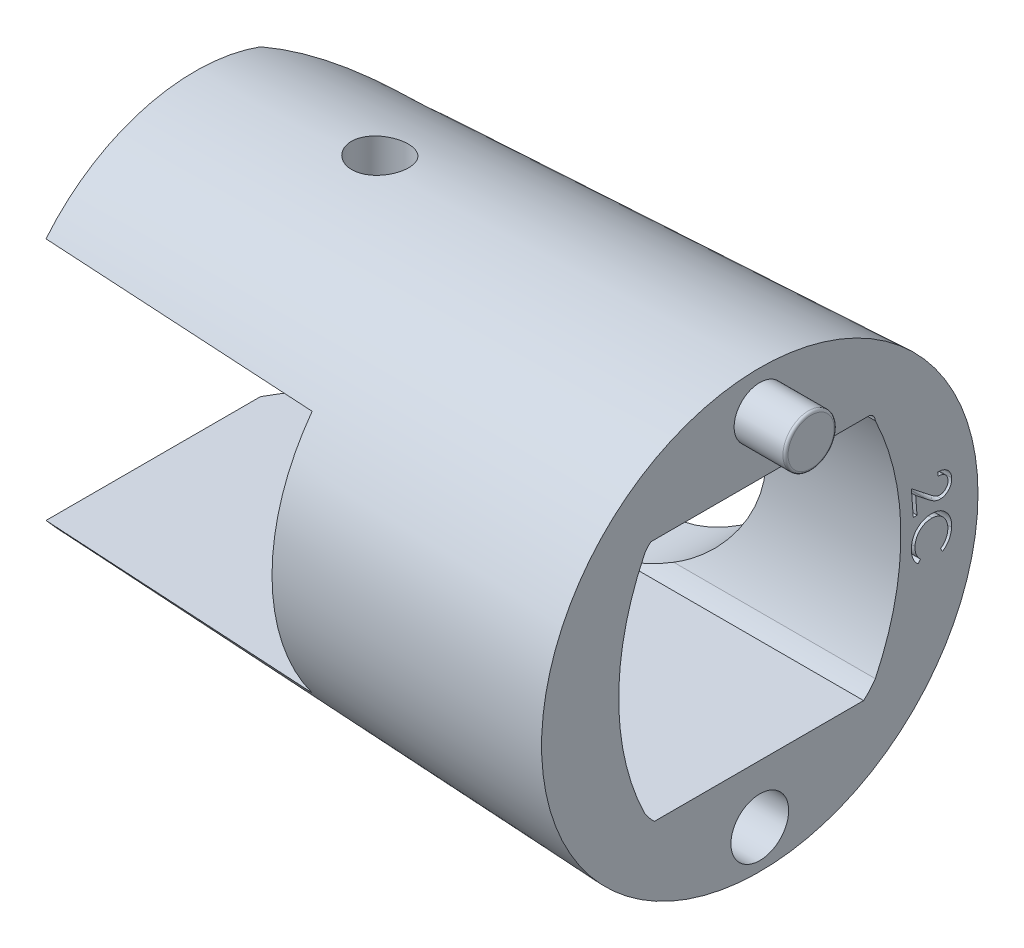
SolidWorks part; units mm, degrees
ref_plane "Front Plane" through (0, 0, 0) normal (0, 0, 1) x (1, 0, 0)
ref_plane "Top Plane" through (0, 0, 0) normal (0, 1, 0) x (1, 0, 0)
ref_plane "Right Plane" through (0, 0, 0) normal (1, 0, 0) x (0, 0, -1)
sketch "Sketch1" plane through (0, 0, 0) normal (0, 1, 0) x (1, 0, 0)
  line L0 (0, 0) -> (-22, 0)
  dimension "D1" = 22
ref_plane "Plane1" through (-22, 0, 0) normal (1, 0, 0) x (0, 0, -1)
sketch "Sketch2" plane through (-22, 0, 0) normal (1, 0, 0) x (0, 0, -1)
  circle A0 centre (0, 0) radius 7.5
  dimension "D1" = 15
sketch "Sketch3" plane through (0, 0, 0) normal (1, 0, 0) x (0, 0, -1)
  circle A0 centre (0, 0) radius 8.5
  dimension "D1" = 17
loft "Loft1" add profiles "Sketch2", "Sketch3" connector at (-22, 0, -7.5) connector at (0, 0, -8.5)
sketch "Sketch4" plane through (0, 0, 0) normal (0, 0, 1) x (1, 0, 0)
  line L0 (0, 0) -> (-10, 0) construction
  line L1 (-26.5378, 4.75) -> (-11, 4.75)
  line L2 (-26.5378, 4.75) -> (-26.5378, -4.75)
  line L3 (-26.5378, -4.75) -> (-11, -4.75)
  line L4 (-11, 4.75) -> (-11, -4.75)
  line L5 (0, 0) -> (-22, 0) construction
  line L6 (0, -8.5) -> (0, 8.5) construction
  point P12 (-11, 0)
  dimension "D1" = 10
  dimension "D2" = 11
  dimension "D3" = 9.5
  dimension "D4" = 15.5378
extrude "Cut-Extrude1" cut sketch "Sketch4" against normal blind 10 and the other way blind 10
sketch "Sketch5" plane through (0, 0, 0) normal (0, 1, 0) x (1, 0, 0)
  line L1 (-11, -6.7777) -> (-23.0023, -6.0429)
  line L2 (-23.0023, -6.0429) -> (-23.0231, -1.4883)
  line L3 (-11, 6.9546) -> (-14.8219, 6.8903)
  line L4 (-11, 8.5741) -> (-11, -8.5015)
  line L7 (-26, -8.5015) -> (-11, -8.5015)
  line L8 (0, 0) -> (-4.8047, 0) construction
  line L9 (0, 8.5) -> (-11, 8.5741) construction
  line L10 (0, -8.5) -> (-11, -8.5015) construction
  line L11 (-26, 8.5015) -> (-11, 8.5015)
  line L12 (-26, 8.5015) -> (-26, -8.5015)
  arc A0 (-14.8219, 6.8903) -> (-23.0231, -1.4883) centre (-14.6815, -1.4502) ccw
  dimension "D4" = 8.3417
  dimension "D11" = 3.8219
  dimension "D1" = 86.496
  dimension "D2" = 89.035
  dimension "D3" = 93.765
  dimension "D5" = 12.0231
  dimension "D6" = 4.5546
  dimension "D7" = 15
  dimension "D8" = 11
  dimension "D9" = 12.0023
  dimension "D10" = 17.003
  dimension "D12" = 1.7238
extrude "Cut-Extrude2" cut sketch "Sketch5" against normal blind 10 and the other way blind 10 contours A0 L3 L7 L1 L2 region at (-11.2267, 0, 7.6396)
sketch "Sketch6" plane through (0, 0, 0) normal (0, 1, 0) x (1, 0, 0)
  line L0 (-11, -8) -> (-15.3, -8) construction
  line L1 (-15.3, 0.5) -> (-15.3, -8) construction
  circle A0 centre (-15.3, 0.5) radius 1.05
  dimension "D1" = 2.1
  dimension "D2" = 4.3
  dimension "D3" = 8.5
extrude "Cut-Extrude3" cut sketch "Sketch6" against normal through all both and the other way through all
sketch "Sketch7" plane through (0, 0, 0) normal (1, 0, 0) x (0, 0, -1)
  line L2 (0, 25.5) -> (0, -8.5) construction
  line L5 (-8.5, 0) -> (8.5, 0) construction
  line L6 (4.3126, 4.2776) -> (4.3126, -4.2776)
  line L7 (-4.3126, 4.2776) -> (-4.3126, -4.2776)
  arc A2 (4.3126, 4.2776) -> (-4.3126, 4.2776) centre (0, -5.2323) ccw
  circle A4 centre (0, 0) radius 8.5 construction
  arc A5 (4.3126, -4.2776) -> (-4.3126, -4.2776) centre (0, 5.2323) cw
  point P11 (-4.3126, 0)
  point P13 (0, 8.5)
  point P16 (0, 0)
  point P17 (4.3126, 0)
  dimension "D3" = 10.4421
  dimension "D1" = 4.2776
  dimension "D2" = 4.3126
sketch "Sketch8" plane through (0, 0, 0) normal (1, 0, 0) x (0, 0, -1)
  line L2 (-4.5, 4.439) -> (4.5, 4.461)
  line L3 (-4.5, -4.261) -> (4.5, -4.239)
  line L4 (-8.5, 0) -> (8.5, 0) construction
  line L5 (0, -8.5) -> (0, 8.7) construction
  line L6 (0, 8.7) -> (0, 5.4132) construction
  line L7 (-4.5, 4.439) -> (-4.5, -4.261) construction
  line L8 (4.5, 4.461) -> (4.5, -4.239) construction
  arc A2 (-4.5, 4.439) -> (-4.5, -4.261) centre (4.5043, 0.089) ccw
  arc A3 (4.5, 4.461) -> (4.5, -4.239) centre (-4.5043, 0.111) cw
  dimension "D1" = 10
  dimension "D7" = 8.5
  dimension "D9" = 4
  dimension "D2" = 9
  dimension "D3" = 4.5
  dimension "D4" = 8.7
  dimension "D5" = 8.7
  dimension "D6" = 4.25
  dimension "D8" = 4.25
  dimension "D10" = 4
extrude "Cut-Extrude4" cut sketch "Sketch8" against normal blind 12 and the other way through all
sketch "Croquis1" plane through (0, 0, 0) normal (1, 0, 0) x (0, 0, -1)
  line L0 (0, 8.5) -> (0, -8.5) construction
  line L2 (-8.5, 0) -> (8.5, 0) construction
  line L3 (9.4094, 0) -> (-9.4094, 0) construction
  circle A0 centre (0, 0) radius 8.5 construction
  circle A1 centre (0, -7) radius 1.125
  circle A2 centre (0, 7) radius 1
  point P4 (0, 0)
  point P13 (0, 0)
  dimension "D2" = 2.25
  dimension "D4" = 2
  dimension "D1" = 1.5
  dimension "D3" = 1.5
extrude "Saliente-Extruir1" add sketch "Croquis1" along normal blind 2 contours A2
extrude "Cortar-Extruir1" cut sketch "Croquis1<4>" against normal blind 2.15 contours A1
sketch "Croquis1<4>" plane through (0, 0, 0) normal (1, 0, 0) x (0, 0, -1) same geometry as "Croquis1"
fillet "Redondeo1" radius 0.1 1 edges at (2, 7, -1)
ref_plane "Plano1" through (0, 0, -8) normal (0, 0, 1) x (1, 0, 0)
sketch "Croquis2" plane through (0, 0, -8) normal (0, 0, 1) x (1, 0, 0)
  line L0 (-11, 4.75) -> (-11, -4.75)
  line L1 (-11, 4.75) -> (-10, 4.75)
  line L2 (-10, -4.75) -> (-11, -4.75)
  arc A0 (-10, 4.75) -> (-10, -4.75) centre (-10, 0) cw
  point P0 (-9.2775, 3.6345)
  point P1 (-8.2353, -5.1333)
  point P2 (-11, 4.75)
  point P3 (-11, -4.75)
  dimension "D1" = 1
extrude "Cortar-Extruir2" cut sketch "Croquis2" along normal mid plane 10
sketch "Croquis8" plane through (-11, 0, 0) normal (-1, 0, 0) x (0, 0, 1)
  line L0 (5.8041, 4.75) -> (-2.5526, 4.75) construction
  line L1 (-6.0137, 4.75) -> (-2.5526, 4.75) construction
  line L2 (-3, 4.4574) -> (4.5, 4.439) construction
  line L3 (-3, 4.75) -> (-3, 4.4574) construction
  line L4 (4.2309, 4.75) -> (-2.5526, 4.75)
  line L5 (-3, 4.75) -> (-2.5526, 4.75)
  line L6 (-3, 4.4574) -> (4.5, 4.439)
  line L7 (-3, 4.75) -> (-3, 4.4574)
  line L8 (6.4372, 4.75) -> (-3, 4.75) construction
  arc A0 (4.5, 4.439) -> (4.2309, 4.75) centre (3.8402, 4.14) ccw
  dimension "D2" = 6.7835
  dimension "D1" = 0.7244
extrude "Cortar-Extruir9" cut sketch "Croquis8" against normal mid plane 40
sketch "Croquis9" plane through (-11, 0, 0) normal (-1, 0, 0) x (0, 0, 1)
  line L0 (6.4372, -4.75) -> (-3, -4.75) construction
  line L1 (-3, -4.2427) -> (-3, -4.75) construction
  line L2 (4.5, -4.261) -> (-3, -4.2427) construction
  line L3 (4.1093, -4.75) -> (-3, -4.75)
  line L4 (-3, -4.2427) -> (-3, -4.75)
  line L5 (4.5, -4.261) -> (-3, -4.2427)
  arc A0 (4.5, -4.261) -> (4.1093, -4.75) centre (2.2668, -2.8774) cw
  dimension "D1" = 7.1093
  dimension "D2" = 2.6271
extrude "Cortar-Extruir10" cut sketch "Croquis9" against normal mid plane 40
sketch "Croquis10" plane through (-22, 0, 0) normal (-1, 0, 0) x (0, 0, 1)
  line L0 (-2.5526, -4.75) -> (-6.0137, -4.75) construction
  line L1 (-3, -4.2427) -> (-4.5, -4.239) construction
  line L2 (-3, -4.75) -> (-3, -4.2427) construction
  line L3 (-3, -4.75) -> (-4.0445, -4.75)
  line L4 (-3, -4.2427) -> (-4.5, -4.239)
  line L5 (-3, -4.75) -> (-3, -4.2427)
  line L6 (-3, -4.75) -> (-6.4936, -4.75) construction
  arc A0 (-4.5, -4.239) -> (-4.0445, -4.75) centre (-2.2631, -2.7036) ccw
  dimension "D2" = 2.7132
  dimension "D1" = 1.0445
extrude "Cortar-Extruir11" cut sketch "Croquis10" against normal mid plane 52
sketch "Croquis11" plane through (-22, 0, 0) normal (-1, 0, 0) x (0, 0, 1)
  line L0 (-3, 4.4574) -> (-3, 4.75) construction
  line L1 (-3, 4.4574) -> (-3, 4.75)
  line L6 (-3, 4.75) -> (-6.4936, 4.75) construction
  line L7 (-4.5, 4.461) -> (-3, 4.4574) construction
  line L8 (-3, 4.75) -> (-4.2831, 4.75)
  line L9 (-4.5, 4.461) -> (-3, 4.4574)
  line L10 (-6.0137, 4.75) -> (-2.5526, 4.75) construction
  arc A0 (-4.5, 4.461) -> (-4.2831, 4.75) centre (-4.1897, 4.4541) cw
  dimension "D2" = 0.3103
extrude "Cortar-Extruir12" cut sketch "Croquis11" against normal mid plane 65
sketch "Croquis12" plane through (0, 0, 0) normal (1, 0, 0) x (0, 0, -1)
  arc A2 (4.9502, -4.4565) -> (4.9502, 4.6785) centre (-4.5043, 0.111) ccw
  arc A3 (4.9502, -4.4565) -> (4.9502, 4.6785) centre (-4.5043, 0.111) ccw construction
  text T0 "2C" font "Century Gothic" height 1.5
  dimension "D1" = 0.5
extrude "Cortar-Extruir13" cut sketch "Croquis12" against normal blind 2
